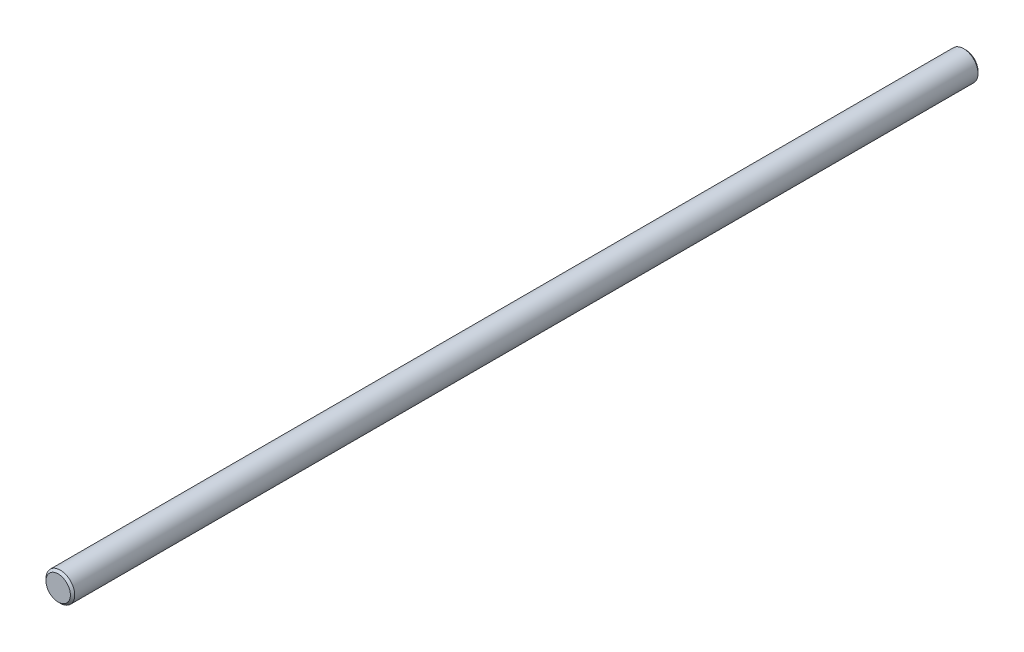
SolidWorks part; units mm, degrees
ref_plane "Front Plane" through (0, 0, 0) normal (0, 0, 1) x (1, 0, 0)
ref_plane "Top Plane" through (0, 0, 0) normal (0, 1, 0) x (1, 0, 0)
ref_plane "Right Plane" through (0, 0, 0) normal (1, 0, 0) x (0, 0, -1)
sketch "Sketch1" plane through (0, 0, 0) normal (1, 0, 0) x (0, 0, -1)
  line L0 (76.2, 0) -> (-76.2, 0) construction
  line L1 (-76.2, -2.413) -> (-76.2, 2.413) construction
  line L2 (-76.2, 2.413) -> (-77.2583, 2.413) construction
  line L3 (76.2, 2.413) -> (76.2, -2.413) construction
  point P3 (76.2, 2.413)
  point P4 (0, 0)
  point P7 (-76.2, 0)
  point P8 (-73.5542, -2.413)
  point P12 (-68.961, 2.413)
  point P13 (76.2, 0)
  point P15 (68.961, 2.413)
  point P19 (-1.0583, -2.413)
  dimension "OD" = 4.826
  dimension "Pitch" = 1.0583
  dimension "Length" = 152.4
  dimension "D1" = 2.6458
  dimension "D4" = 7.239
  dimension "D5" = 7.239
  dimension "SL" = 75.1417
sketch "Sketch2" plane through (0, 0, 0) normal (0, 0, 1) x (1, 0, 0)
  line L0 (0, -2.413) -> (0, 2.413) construction
  line L1 (-2.413, 0) -> (2.413, 0) construction
  circle A0 centre (0, 0) radius 2.413
extrude "Boss-Extrude1" add sketch "Sketch2" along normal up to vertex (76.2 mm away) and the other way up to vertex (76.2 mm away) up to point (0, 0, 76.2) other way up to point (0, 0, -76.2)
chamfer "Chamfer1" distance 0.3619 angle 45 2 edges at (2.413, 0, -76.2) (2.413, 0, 76.2)
ref_axis "Center Axis 1" through (0, 0, -76.2) along (0, 0, 1)
sketch "Sketch13" plane through (0, 0, 76.2) normal (0, 0, 1) x (1, 0, 0)
  circle A0 centre (0, 0) radius 2.413
curve "Helix/Spiral1" pitch 1.0583 height 76.2 turns 72
sketch "Sketch14" plane through (0, 0, 0) normal (1, 0, 0) x (0, 0, -1)
  line L0 (-77.1922, 2.5276) -> (-76.663, 1.611) construction
  line L1 (-76.663, 1.611) -> (-76.1339, 2.5276) construction
  line L2 (-76.1339, 2.5276) -> (-77.1922, 2.5276) construction
  line L3 (-76.663, 2.5276) -> (-76.663, 2.413) construction
  line L4 (-76.663, 2.413) -> (-76.663, 1.7256) construction
  line L5 (-76.663, 1.7256) -> (-76.663, 1.611) construction
  line L6 (-77.126, 2.413) -> (-76.2, 2.413) construction
  line L8 (-76.1669, 2.4703) -> (-77.1591, 2.4703) construction
  line L9 (-76.7292, 1.7256) -> (-76.5969, 1.7256)
  line L10 (-76.7292, 1.7256) -> (-76.5969, 1.7256) construction
  line L11 (-76.5969, 1.7256) -> (-76.1669, 2.4703)
  line L12 (-76.1669, 2.4703) -> (-77.1591, 2.4703)
  line L13 (-77.1591, 2.4703) -> (-76.7292, 1.7256)
  point P9 (-76.663, 1.7256)
  point P14 (-76.663, 2.413)
  point P16 (-76.663, 2.4703)
  point P17 (-76.663, 2.4703)
  dimension "D1" = 1.0583
  dimension "D2" = 0.1323
sweep "Cut-Sweep1" [suppressed] cut profiles "Sketch14" path "Helix/Spiral1"
pattern_linear "LPattern1" [suppressed] count 3 spacing 75.1417 along (0, 0, -1) of bodies 503
equation "\"D1@Chamfer1\"=\"OD@Sketch1\"*.075"
equation "\"D4@Sketch1\"=\"OD@Sketch1\"*1.5"
equation "\"D5@Sketch1\"=\"OD@Sketch1\"*1.5"
equation "\"SL@Sketch1\"=\"Pitch@Sketch1\"*71"
equation "\"D4@Helix/Spiral1\"=\"Pitch@Sketch1\""
equation "\"D5@Helix/Spiral1\"= ( \"SL@Sketch1\" / \"Pitch@Sketch1\" ) + 1"
equation "\"D1@Sketch14\"=\"Pitch@Sketch1\""
equation "\"D2@Sketch14\"=\"D1@Sketch14\"/8"
equation "\"D3@LPattern1\"=\"SL@Sketch1\""
equation "\"D1@Sketch1\"=\"Pitch@Sketch1\"*2.5"
